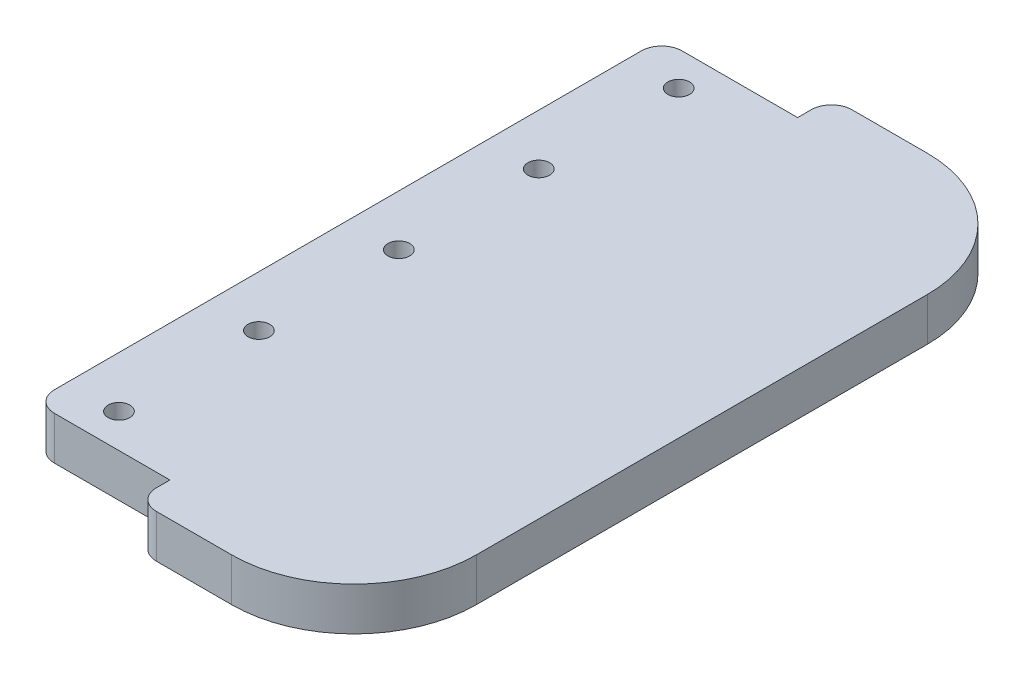
SolidWorks part; units mm, degrees
ref_plane "Front Plane" through (0, 0, 0) normal (0, 0, 1) x (1, 0, 0)
ref_plane "Top Plane" through (0, 0, 0) normal (0, 1, 0) x (1, 0, 0)
ref_plane "Right Plane" through (0, 0, 0) normal (1, 0, 0) x (0, 0, -1)
sketch "Sketch1" plane through (0, 0, 0) normal (0, 1, 0) x (1, 0, 0)
  line L0 (7.5, 102.362) -> (7.5, 0) construction
  line L1 (0, 0) -> (52.084, 0)
  line L2 (0, 0) -> (0, 102.362)
  line L3 (0, 102.362) -> (52.084, 102.362)
  line L4 (52.084, 0) -> (52.084, 102.362)
  line L6 (20, 0) -> (0, 0)
  line L7 (20, 0) -> (20, 5)
  line L8 (20, 5) -> (0, 5)
  line L9 (0, 0) -> (0, 5)
  line L10 (0, 102.362) -> (20, 102.362)
  line L11 (0, 102.362) -> (0, 97.362)
  line L12 (0, 97.362) -> (20, 97.362)
  line L13 (20, 102.362) -> (20, 97.362)
  circle A0 centre (38.876, 95.63) radius 3.45
  circle A1 centre (38.876, 51.18) radius 11.684
  circle A2 centre (38.876, 6.73) radius 3.45
  circle A3 centre (7.5, 92.362) radius 1.6
  circle A4 centre (7.5, 71.772) radius 1.6
  circle A5 centre (7.5, 51.182) radius 1.6
  circle A6 centre (7.5, 30.592) radius 1.6
  circle A7 centre (7.5, 10.002) radius 1.6
  dimension "D4" = 6.9
  dimension "D5" = 23.368
  dimension "D11" = 3.2
  dimension "D1" = 102.362
  dimension "D2" = 52.084
  dimension "D6" = 44.45
  dimension "D7" = 44.45
  dimension "D8" = 51.18
  dimension "D9" = 13.208
  dimension "D10" = 7.5
  dimension "D12" = 10
  dimension "D14" = 20
  dimension "D15" = 5
  dimension "D18" = 20.59
  dimension "D13" = 5
extrude "Boss-Extrude1" add sketch "Sketch1" along normal blind 6.35 contours L1 L4 L3 L2
extrude "Cut-Extrude2" cut sketch "Sketch1<4>" along normal through all contours A4 L0 | L0 A4 | A3 | A5 | A6 | A7 region at (8.1791, 0, -71.772) region at (6.8209, 0, -71.772)
sketch "Sketch1<4>" plane through (0, 0, 0) normal (0, 1, 0) x (1, 0, 0) same geometry as "Sketch1"
extrude "Cut-Extrude3" cut sketch "Sketch1<5>" along normal offset from surface (4.7625 mm away) 1.5875 contours A1 | A0 | A2 region at (38.876, 0, -95.63) region at (38.876, 0, -51.18) up to face at (7.5, 6.35, -8.402)
sketch "Sketch1<5>" plane through (0, 0, 0) normal (0, 1, 0) x (1, 0, 0) same geometry as "Sketch1"
fillet "Fillet1" radius 18 2 edges at (52.084, 3.175, -102.362) (52.084, 3.175, 0)
extrude "Cut-Extrude4" cut sketch "Sketch1<7>" along normal through all contours L6 L7 L8 L9 | L10 L13 L12 L11
sketch "Sketch1<7>" plane through (0, 0, 0) normal (0, 1, 0) x (1, 0, 0) same geometry as "Sketch1"
fillet "Fillet4" radius 3 4 edges at (20, 3.175, -102.362) (0, 3.175, -97.362) (0, 3.175, -5) (20, 3.175, 0)
